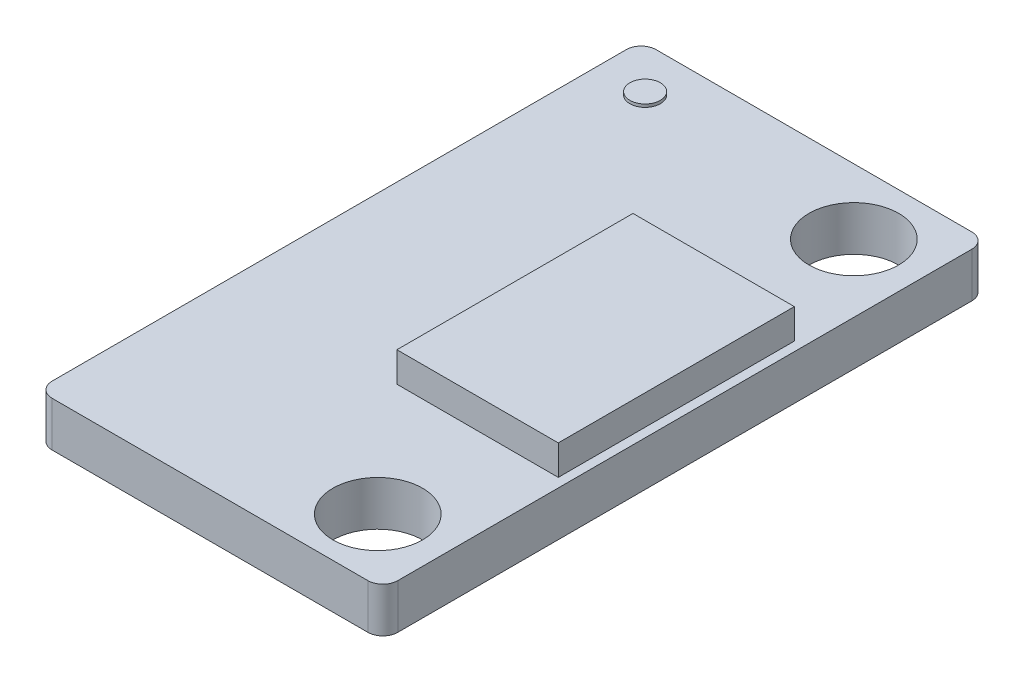
SolidWorks part; units mm, degrees
ref_plane "Front Plane" through (0, 0, 0) normal (0, 0, 1) x (1, 0, 0)
ref_plane "Top Plane" through (0, 0, 0) normal (0, 1, 0) x (1, 0, 0)
ref_plane "Right Plane" through (0, 0, 0) normal (1, 0, 0) x (0, 0, -1)
sketch "Sketch1" plane through (0, 0, 0) normal (0, 1, 0) x (1, 0, 0)
  line L0 (69.2617, 243.164) -> (402.595, 243.164) construction
  line L1 (-2.7, 3.95) -> (2.7, 3.95)
  line L2 (-2.7, 3.95) -> (-2.7, -3.95)
  line L3 (-2.7, -3.95) -> (2.7, -3.95)
  line L4 (2.7, 3.95) -> (2.7, -3.95)
  line L5 (-2.7, 3.95) -> (2.7, -3.95) construction
  line L6 (-2.7, -3.95) -> (2.7, 3.95) construction
  line L8 (-8.5604, 10.0844) -> (3.006, 10.0844)
  line L9 (-8.5604, 10.0844) -> (-8.5604, -10.1269)
  line L10 (-8.5604, -10.1269) -> (3.006, -10.1269)
  line L11 (3.006, 10.0844) -> (3.006, -10.1269)
  circle A8 centre (-6.9301, 8.5864) radius 0.51
  point P0 (0, 0)
  point P8 (2.7, -3.95)
  dimension "D3" = 1.02
  dimension "D1" = 5.4
  dimension "D2" = 7.9
  dimension "D4" = 6.9301
  dimension "D5" = 8.5864
  dimension "D6" = 20.2113
  dimension "D7" = 10.0844
  dimension "D8" = 11.5664
  dimension "D9" = 8.5604
extrude "Boss-Extrude1" add sketch "Sketch1" against normal blind 1.5 contours L8 L11 L10 L9
extrude "Boss-Extrude2" add sketch "Sketch1<4>" along normal blind 1 contours L1 L4 L3 L2
sketch "Sketch1<4>" plane through (0, 0, 0) normal (0, 1, 0) x (1, 0, 0) same geometry as "Sketch1"
extrude "Boss-Extrude3" add sketch "Sketch1<5>" along normal blind 0.1 contours A8
sketch "Sketch1<5>" plane through (0, 0, 0) normal (0, 1, 0) x (1, 0, 0) same geometry as "Sketch1"
sketch "Sketch2" plane through (0, 0, 0) normal (0, 1, 0) x (1, 0, 0)
  line L0 (-8.5604, -10.1269) -> (3.006, -10.1269) construction
  line L1 (3.006, 10.0844) -> (3.006, -10.1269) construction
  circle A0 centre (0.7417, 7.8995) radius 1.5
  circle A1 centre (0.7417, -8.0329) radius 1.5
  point P8 (0, 0)
  dimension "D1" = 3
  dimension "D2" = 3
  dimension "D3" = 15.9324
  dimension "D4" = 2.094
  dimension "D5" = 2.2642
extrude "Cut-Extrude1" cut sketch "Sketch2" against normal blind 2.1
fillet "Fillet1" radius 0.5 4 edges at (3.006, -0.75, -10.0844) (-8.5604, -0.75, -10.0844) (-8.5604, -0.75, 10.1269) (3.006, -0.75, 10.1269)
